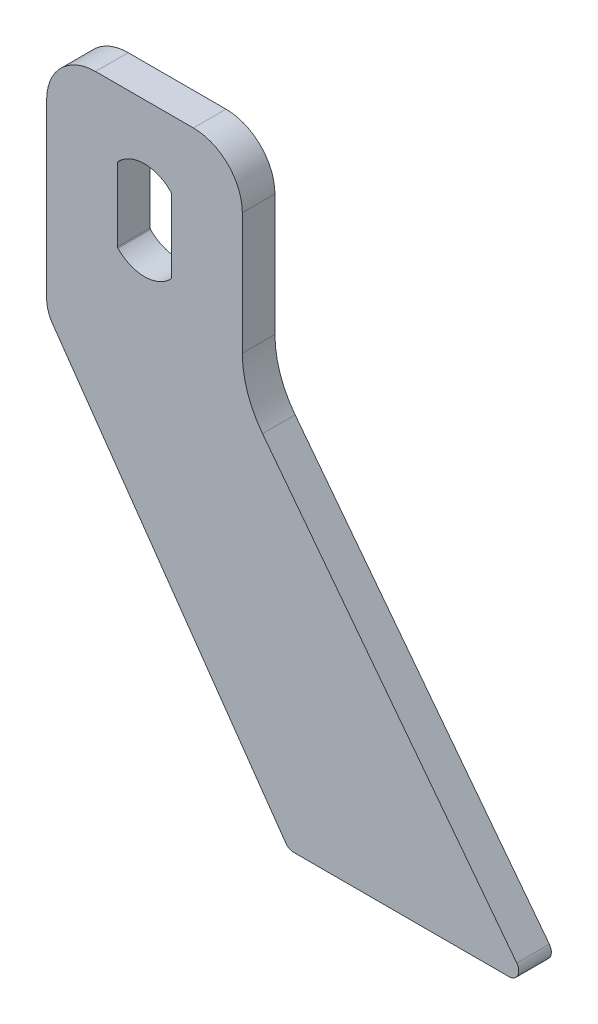
SolidWorks part; units mm, degrees
ref_plane "Plane1" through (0, 0, 0) normal (0, 0, 1) x (1, 0, 0)
ref_plane "Plane2" through (0, 0, 0) normal (0, 1, 0) x (1, 0, 0)
ref_plane "Plane3" through (0, 0, 0) normal (1, 0, 0) x (0, 0, -1)
sketch "Sketch1" plane through (0, 0, 0) normal (0, 0, 1) x (1, 0, 0)
  line L0 (0, 0) -> (0, 28.0485) construction
  line L1 (0, 0) -> (0, 18.0801) construction
  line L2 (0, 0) -> (8.25, 0) construction
  line L3 (8.25, -11.1998) -> (8.25, 11.1998)
  line L4 (15, 32) -> (-15, 32)
  line L5 (-30, 17) -> (-30, -35.847)
  line L6 (-28.1915, -41.5828) -> (43.3262, -143.7207)
  line L10 (30, 17) -> (30, -20.3164)
  line L11 (36.1994, -38.5792) -> (114.1556, -140.1737)
  line L12 (-8.25, -11.1998) -> (-8.25, 11.1998)
  line L13 (45.7837, -145) -> (111.7755, -145)
  arc A0 (8.1105, 11.5463) -> (-8.1105, 11.5463) centre (0, 3.75) ccw
  arc A1 (8.1105, -11.5463) -> (-8.1105, -11.5463) centre (0, -3.75) cw
  arc A2 (-15, 32) -> (-30, 17) centre (-15, 17) ccw
  arc A3 (15, 32) -> (30, 17) centre (15, 17) cw
  arc A4 (8.25, 11.1998) -> (8.1105, 11.5463) centre (7.75, 11.1998) ccw
  arc A5 (-8.25, 11.1998) -> (-8.1105, 11.5463) centre (-7.75, 11.1998) cw
  arc A6 (-8.1105, -11.5463) -> (-8.25, -11.1998) centre (-7.75, -11.1998) cw
  arc A7 (8.1105, -11.5463) -> (8.25, -11.1998) centre (7.75, -11.1998) ccw
  arc A8 (-30, -35.847) -> (-28.1915, -41.5828) centre (-20, -35.847) ccw
  arc A9 (30, -20.3164) -> (36.1994, -38.5792) centre (60, -20.3164) ccw
  arc A10 (111.7755, -145) -> (114.1556, -140.1737) centre (111.7755, -142) ccw
  arc A11 (45.7837, -145) -> (43.3262, -143.7207) centre (45.7837, -142) cw
  point P23 (30, 32)
  point P25 (-8.25, 0)
  point P27 (8.25, 11.3985)
  point P30 (-8.25, 11.3985)
  point P33 (-8.25, -11.3985)
  point P36 (8.25, -11.3985)
  point P38 (-30, -39)
  point P42 (30, -30.5)
  dimension "D3" = 35
  dimension "D13" = 15
  dimension "D2" = 16.5
  dimension "D8" = 30
  dimension "D14" = 11.25
  dimension "D15" = 0.5
  dimension "D16" = 10
  dimension "D18" = 30
  dimension "D10" = 3
  dimension "D4" = 30
  dimension "D5" = 60
  dimension "D6" = 32
  dimension "D7" = 37.5
  dimension "D9" = 177
  dimension "D12" = 71
  dimension "D17" = 62.5
extrude "Extrude1" add sketch "Sketch1" along normal blind 10
ref_axis "Hul center" through (0, 0, 0) along (0, 0, 1)
